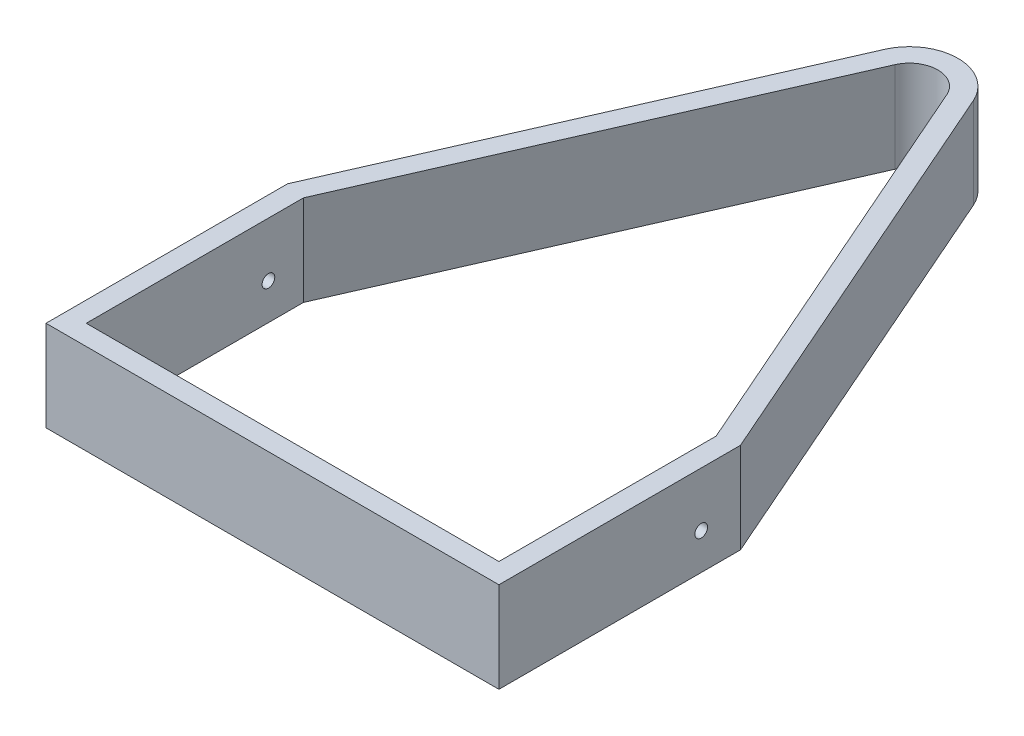
SolidWorks part; units mm, degrees
ref_plane "Front Plane" through (0, 0, 0) normal (0, 0, 1) x (1, 0, 0)
ref_plane "Top Plane" through (0, 0, 0) normal (0, 1, 0) x (1, 0, 0)
ref_plane "Right Plane" through (0, 0, 0) normal (1, 0, 0) x (0, 0, -1)
sketch "Sketch1" plane through (0, 0, 0) normal (0, 1, 0) x (1, 0, 0)
  line L0 (-71.4375, 0) -> (71.4375, 0)
  line L1 (-71.4375, 38.1) -> (71.4375, 38.1) construction
  line L2 (-71.4375, 0) -> (-71.4375, 76.2)
  line L3 (-71.4375, 38.1) -> (0, 200.9175) construction
  line L8 (0, 200.9175) -> (71.4375, 38.1) construction
  line L13 (71.4375, 0) -> (71.4375, 76.2)
  line L14 (-71.4375, 76.2) -> (-14.0181, 207.068)
  line L15 (14.0181, 207.068) -> (71.4375, 76.2)
  line L16 (-65.0875, 6.35) -> (-65.0875, 74.8682)
  line L17 (-65.0875, 74.8682) -> (-8.2032, 204.5167)
  line L18 (8.2032, 204.5167) -> (65.0875, 74.8682)
  line L19 (65.0875, 6.35) -> (65.0875, 74.8682)
  line L20 (-65.0875, 6.35) -> (65.0875, 6.35)
  arc A0 (-14.0181, 207.068) -> (14.0181, 207.068) centre (0, 200.9175) cw
  arc A2 (-8.2032, 204.5167) -> (8.2032, 204.5167) centre (0, 200.9175) cw
  point P4 (0, 0)
  dimension "D1" = 142.875
  dimension "D2" = 177.8
  dimension "D3" = 38.1
  dimension "D4" = 76.2
  dimension "D6" = 6.35
extrude "Boss-Extrude1" add sketch "Sketch1" along normal blind 28.575
sketch "Sketch2" plane through (0, 0, 0) normal (1, 0, 0) x (0, 0, -1)
  line L4 (74.8682, 28.575) -> (74.8682, 0) construction
  line L5 (0, 0) -> (76.2, 0) construction
  circle A0 centre (63.8192, 11.43) radius 11.049 construction
  circle A1 centre (63.8192, 11.43) radius 2
  dimension "D1" = 22.098
  dimension "D2" = 4
  dimension "D3" = 11.43
extrude "Cut-Extrude1" cut sketch "Sketch2" against normal up to next from surface starting at face at (-65.0875, 14.2875, -40.6091)
extrude "Cut-Extrude3" cut sketch "Sketch2<2>" along normal up to next from surface starting at face at (65.0875, 14.2875, -40.6091)
sketch "Sketch2<2>" plane through (0, 0, 0) normal (1, 0, 0) x (0, 0, -1) same geometry as "Sketch2"
